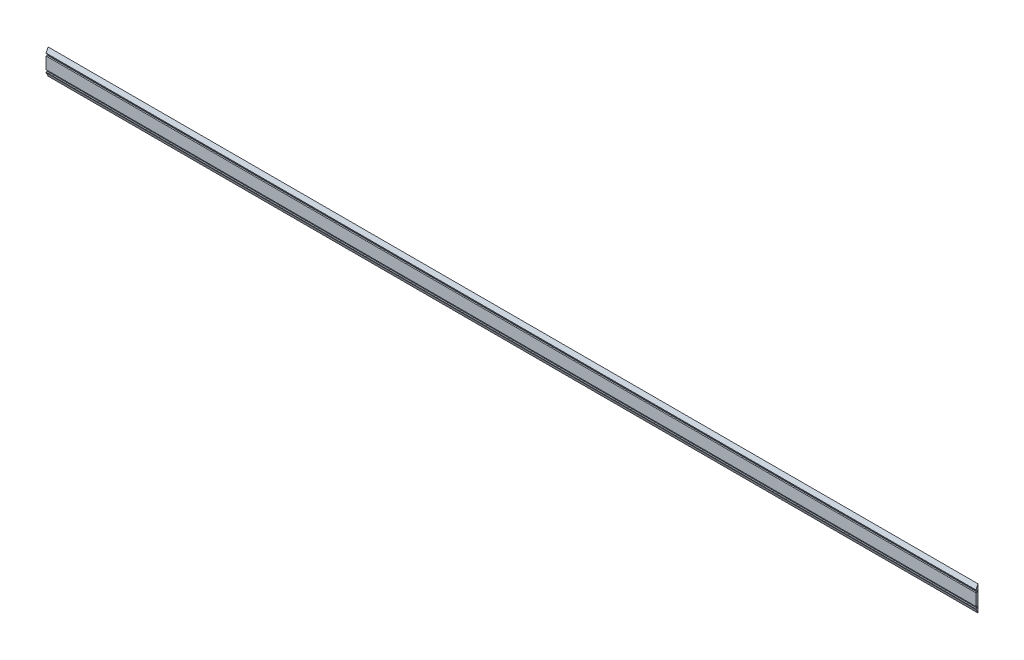
SolidWorks part; units mm, degrees
ref_plane "Спереди" through (0, 0, 0) normal (0, 0, 1) x (1, 0, 0)
ref_plane "Сверху" through (0, 0, 0) normal (0, 1, 0) x (1, 0, 0)
ref_plane "Справа" through (0, 0, 0) normal (1, 0, 0) x (0, 0, -1)
sketch "Эскиз1" plane through (0, 0, 0) normal (0, 0, 1) x (1, 0, 0)
  line L1 (0, -60) -> (2200, -60)
  line L2 (0, -60) -> (0, 0)
  line L3 (0, 0) -> (2200, 0)
  line L4 (2200, -60) -> (2200, 0)
  dimension "D1" = 2200
  dimension "D2" = 60
extrude "Бобышка-Вытянуть1" add sketch "Эскиз1" along normal blind 5
chamfer "Фаска1" distance 5 distance2 10 2 edges at (1100, 0, 5) (1100, -60, 5) first distance on face at (1100, 0, 2.5) first distance on face at (1100, -60, 2.5)
sketch "Эскиз2" plane through (0, 0, 5) normal (0, 0, 1) x (1, 0, 0)
  line L0 (0, -10) -> (0, -50) construction
  line L1 (0, -49) -> (2200, -49)
  line L2 (0, -49) -> (0, -44)
  line L3 (0, -44) -> (2200, -44)
  line L4 (2200, -49) -> (2200, -44)
  line L5 (2200, -50) -> (2200, -10) construction
  line L6 (0, -50) -> (0, -49) construction
  line L7 (2200, -11) -> (0, -11)
  line L8 (2200, -11) -> (2200, -16)
  line L9 (2200, -16) -> (0, -16)
  line L10 (0, -11) -> (0, -16)
  line L11 (0, -10) -> (0, -11) construction
  dimension "D1" = 1
  dimension "D2" = 5
extrude "Вырез-Вытянуть2" cut sketch "Эскиз2" against normal blind 3
